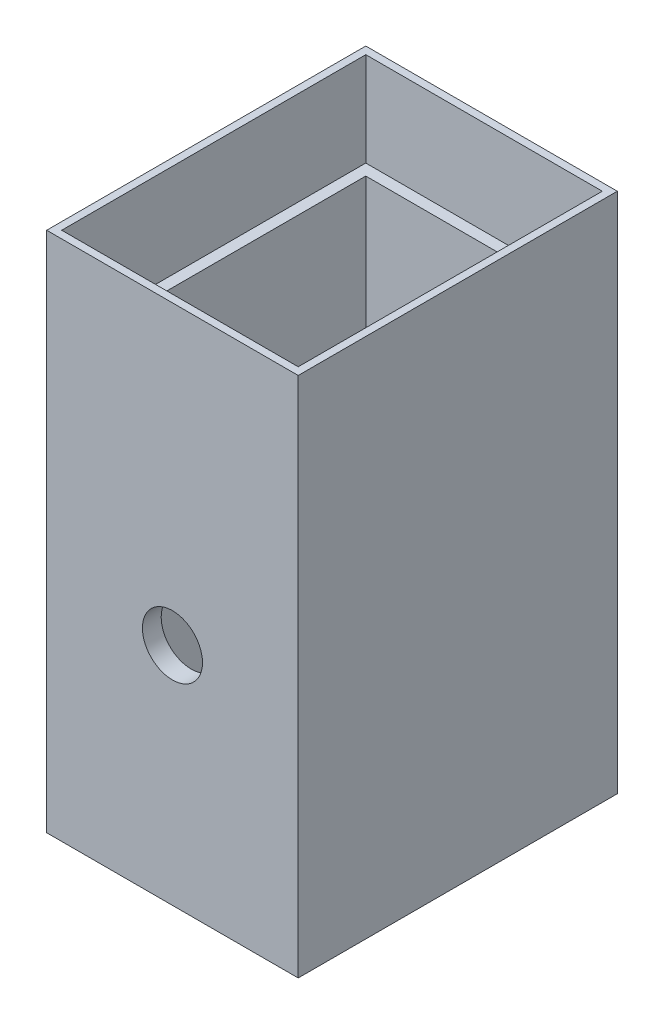
SolidWorks part; units mm, degrees
ref_plane "Front Plane" through (0, 0, 0) normal (0, 0, 1) x (1, 0, 0)
ref_plane "Top Plane" through (0, 0, 0) normal (0, 1, 0) x (1, 0, 0)
ref_plane "Right Plane" through (0, 0, 0) normal (1, 0, 0) x (0, 0, -1)
sketch "Sketch2" plane through (0, 0, 0) normal (0, 1, 0) x (1, 0, 0)
  line L0 (-33.5, 42.5) -> (33.5, 42.5)
  line L1 (-28.5, 37.5) -> (28.5, 37.5)
  line L2 (-28.5, 37.5) -> (-28.5, -37.5)
  line L3 (-28.5, -37.5) -> (28.5, -37.5)
  line L4 (28.5, 37.5) -> (28.5, -37.5)
  line L5 (-28.5, 37.5) -> (28.5, -37.5) construction
  line L6 (-28.5, -37.5) -> (28.5, 37.5) construction
  line L7 (33.5, 42.5) -> (33.5, -42.5)
  line L8 (-33.5, -42.5) -> (33.5, -42.5)
  line L9 (-33.5, 42.5) -> (-33.5, -42.5)
  point P0 (0, 0)
  dimension "D1" = 57
  dimension "D2" = 75
  dimension "D3" = 5
extrude "Boss-Extrude1" add sketch "Sketch2" along normal blind 4 contours L4 L1 L2 L3 | L0 L9 L8 L7 L1 L4 L3 L2 region at (0, 0, -41.4177) region at (0, 0, 0)
extrude "Boss-Extrude2" add sketch "Sketch2<3>" along normal blind 114
sketch "Sketch2<3>" plane through (0, 0, 0) normal (0, 1, 0) x (1, 0, 0) same geometry as "Sketch2"
sketch "Sketch4" plane through (0, 114, 0) normal (0, 1, 0) x (1, 0, 0)
  line L0 (31.5, 40.5) -> (-31.5, 40.5)
  line L1 (-31.5, -40.5) -> (-31.5, 40.5)
  line L2 (33.5, -42.5) -> (-33.5, -42.5)
  line L3 (33.5, -42.5) -> (33.5, 42.5)
  line L4 (33.5, 42.5) -> (-33.5, 42.5)
  line L5 (-33.5, -42.5) -> (-33.5, 42.5)
  line L6 (33.5, -42.5) -> (-33.5, 42.5) construction
  line L7 (33.5, 42.5) -> (-33.5, -42.5) construction
  line L8 (31.5, -40.5) -> (-31.5, -40.5)
  line L9 (31.5, -40.5) -> (31.5, 40.5)
  point P1 (0, 0)
  dimension "D1" = 2
extrude "Boss-Extrude3" add sketch "Sketch4" along normal blind 25
sketch "Sketch5" plane through (0, 0, -42.5) normal (0, 0, -1) x (-1, 0, 0)
  line L0 (33.5, 139) -> (33.5, 0) construction
  line L1 (13.5, 22) -> (23.5, 22)
  line L2 (13.5, 22) -> (13.5, 7)
  line L3 (13.5, 7) -> (23.5, 7)
  line L4 (23.5, 22) -> (23.5, 7)
  line L5 (13.5, 22) -> (23.5, 7) construction
  line L6 (13.5, 7) -> (23.5, 22) construction
  line L7 (33.5, 0) -> (-33.5, 0) construction
  point P0 (18.5, 14.5)
  dimension "D1" = 10
  dimension "D2" = 10
  dimension "D3" = 15
  dimension "D4" = 7
sketch "Sketch6" plane through (0, 0, 42.5) normal (0, 0, 1) x (1, 0, 0)
  line L0 (-33.5, 0) -> (33.5, 0) construction
  line L1 (33.5, 139) -> (33.5, 0) construction
  circle A0 centre (0, 60) radius 8
  dimension "D1" = 16
  dimension "D2" = 60
  dimension "D3" = 33.5
extrude "Cut-Extrude1" cut sketch "Sketch6" against normal blind 25
extrude "Cut-Extrude2" cut sketch "Sketch5" against normal blind 25
